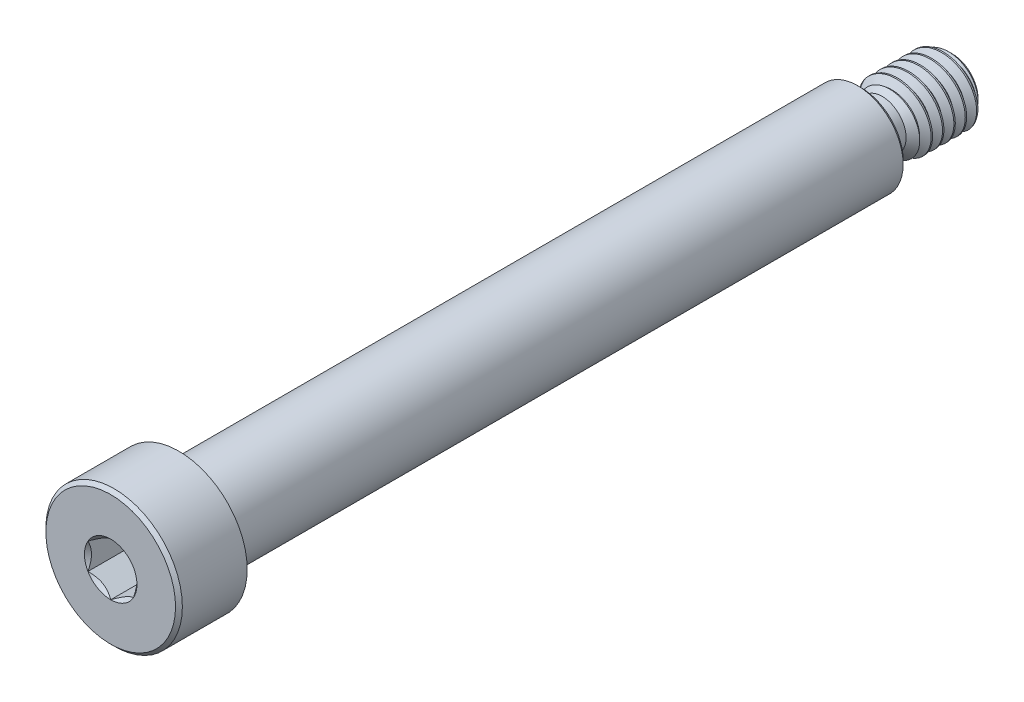
SolidWorks part; units mm, degrees
material "Alloy Steel"
ref_plane "Front Plane" through (0, 0, 0) normal (0, 0, 1) x (1, 0, 0)
ref_plane "Top Plane" through (0, 0, 0) normal (0, 1, 0) x (1, 0, 0)
ref_plane "Right Plane" through (0, 0, 0) normal (1, 0, 0) x (0, 0, -1)
sketch "Sketch2" plane through (0, 0, 0) normal (1, 0, 0) x (0, 0, -1)
  line L0 (-18.5, 0) -> (18.5, 0) construction
  line L1 (-18.5, 0) -> (-18.5, 3)
  line L2 (-18.5, 3) -> (-15.5, 3)
  line L3 (-15.5, 3) -> (-15.5, 2)
  line L4 (-15.5, 2) -> (14.5, 2)
  line L5 (14.5, 1.5) -> (18.5, 1.5)
  line L6 (18.5, 1.5) -> (18.5, 0)
  line L7 (18.4687, 1.5541) -> (18.7187, 1.1211) construction
  line L8 (18.7187, 1.1211) -> (18.9687, 1.5541) construction
  line L9 (18.9687, 1.5541) -> (18.4687, 1.5541) construction
  line L10 (18.5, 1.5) -> (18.9375, 1.5) construction
  line L11 (18.7187, 1.5541) -> (18.7187, 1.5) construction
  line L12 (18.7187, 1.5) -> (18.7187, 1.1752) construction
  line L13 (18.7187, 1.1752) -> (18.7187, 1.1211) construction
  line L14 (18.6875, 1.1752) -> (18.75, 1.1752)
  line L15 (18.4844, 1.5271) -> (18.9531, 1.5271)
  line L16 (18.75, 1.1752) -> (18.9531, 1.5271)
  line L17 (18.6875, 1.1752) -> (18.4844, 1.5271)
  line L18 (18.5, 0) -> (18.5, -1.5) construction
  line L19 (14.5, -2) -> (14.5, 0) construction
  line L20 (14.5, 0) -> (14.5, 2) construction
  line L21 (-18.5, 0) -> (-18.5, -3) construction
  line L22 (15.414, 1.05) -> (15.414, -1.05) construction
  line L23 (18.5, 0) -> (15.414, 0) construction
  ellipse E0 centre (16.957, 0) end of major axis (16.957, 0.6) minor radius 0.6 construction
  point P12 (17.25, -1.5)
  point P22 (18.7187, 1.5271)
  point P23 (10.5, 0)
  point P25 (-10.5, 0)
  point P26 (-15.5, -3)
  point P29 (14.5, -2)
  point P40 (15.414, 0)
  dimension "D1" = 1.25
  dimension "D3" = 8
  dimension "D4" = 8
  dimension "Shoulder Length" = 30
  dimension "D5" = 1.2
  dimension "D6" = 1.2
sketch "Sketch3" plane through (0, 0, 0) normal (0, 0, 1) x (1, 0, 0)
  line L1 (0, 1.1547) -> (-1, 0.5774)
  line L2 (-1, 0.5774) -> (-1, -0.5774)
  line L3 (-1, -0.5774) -> (0, -1.1547)
  line L4 (0, -1.1547) -> (1, -0.5774)
  line L5 (1, -0.5774) -> (1, 0.5774)
  line L6 (1, 0.5774) -> (0, 1.1547)
  circle A0 centre (0, 0) radius 1 construction
  dimension "Drive Size" = 2
sketch "Sketch4" plane through (0, 0, 0) normal (1, 0, 0) x (0, 0, -1)
  line L0 (-15.5, 3) -> (-18.35, 3)
  line L1 (-18.35, 3) -> (-18.5, 2.85)
  line L2 (-15.5, 3) -> (-15.5, 2)
  line L7 (-18.5, 0) -> (18.5, 0) construction
  line L8 (-15.5, 2) -> (14.3333, 2)
  line L9 (14.3333, 2) -> (14.5, 1.8333)
  line L10 (14.5, 1.8333) -> (14.5, 0)
  line L11 (14.5, 2) -> (14.5, 1.8333) construction
  line L12 (14.5, 1.8333) -> (14.5, 1.6667) construction
  line L13 (14.5, 1.6667) -> (14.5, 1.5) construction
  line L14 (-18.5, 2.85) -> (-18.5, 0)
  line L16 (-18.5, 0) -> (14.5, 0)
  line L18 (-18.5, 3) -> (-15.5, 3) construction
  dimension "D3" = 45
  dimension "D5" = 5.7
  dimension "D1" = 45
revolve "Revolve1" add sketch "Sketch4" angle 360 about L16
sketch "Sketch5" plane through (0, 0, 18.5) normal (0, 0, 1) x (1, 0, 0)
  line L0 (1, 0.5774) -> (0, 1.1547) construction
  line L1 (1, -0.5774) -> (1, 0.5774) construction
  line L2 (0, -1.1547) -> (1, -0.5774) construction
  line L3 (-1, -0.5774) -> (0, -1.1547) construction
  line L4 (-1, 0.5774) -> (-1, -0.5774) construction
  line L5 (0, 1.1547) -> (-1, 0.5774) construction
  line L6 (1, 0.5774) -> (0, 1.1547)
  line L7 (1, -0.5774) -> (1, 0.5774)
  line L8 (0, -1.1547) -> (1, -0.5774)
  line L9 (-1, -0.5774) -> (0, -1.1547)
  line L10 (-1, 0.5774) -> (-1, -0.5774)
  line L11 (0, 1.1547) -> (-1, 0.5774)
extrude "Cut-Extrude1" cut sketch "Sketch5" against normal blind 2.25
sketch "Sketch6" plane through (0, 0, 18.5) normal (0, 0, 1) x (1, 0, 0)
  circle A0 centre (0, 0) radius 1.1547
extrude "Cut-Extrude4" cut sketch "Sketch6" against normal blind 2.25 draft 45
sketch "Sketch7" plane through (0, 0, 0) normal (1, 0, 0) x (0, 0, -1)
  line L0 (14.5, 1.5) -> (18.125, 1.5)
  line L1 (14.5, 1.5) -> (18.5, 1.5) construction
  line L2 (18.125, 1.5) -> (18.5, 1.125)
  line L3 (18.5, 1.5) -> (18.5, 0) construction
  line L4 (18.5, 1.125) -> (18.5, 0)
  line L5 (18.5, 0) -> (14.5, 0)
  line L6 (14.5, -1.8333) -> (14.5, 1.8333) construction
  line L7 (14.5, 0) -> (14.5, 1.5)
  dimension "D1" = 45
  dimension "D2" = 0.375
revolve "Revolve2" add sketch "Sketch7" angle 360 about L5
sketch "Sketch10" plane through (0, 0, 0) normal (1, 0, 0) x (0, 0, -1)
  line L0 (14.725, 1.05) -> (15.414, 1.05)
  line L1 (15.414, 1.05) -> (16.364, 2)
  line L2 (16.364, 2) -> (14.5, 2)
  line L3 (14.5, 2) -> (14.5, 1.275)
  line L5 (18.5, 0) -> (14.5, 0) construction
  line L6 (-18.5, 0) -> (18.5, 0) construction
  line L7 (-15.5, 2) -> (14.5, 2) construction
  line L12 (-15.5, 2) -> (-15.1, 2)
  line L13 (-15.5, 2) -> (-15.5, 1.9)
  line L14 (-15.5, 1.9) -> (-15.2, 1.9)
  line L15 (-15.1, 2) -> (-15.2, 1.9)
  line L16 (14.725, 1.05) -> (14.725, 1.275) construction
  line L17 (14.725, 1.275) -> (14.725, 1.5) construction
  line L18 (18.125, 1.5) -> (14.5, 1.5) construction
  arc A0 (14.5, 1.275) -> (14.725, 1.05) centre (14.725, 1.275) ccw
  dimension "D3" = 45
  dimension "D4" = 45
  dimension "D5" = 3.8
  dimension "D1" = 0.3
revolve "Cut-Revolve1" cut sketch "Sketch10" angle 360 about L5
fillet "Fillet1" radius 0.05 1 edges at (-1.9, 0, 15.5)
sketch "Sketch15" plane through (0, 0, 0) normal (0, 0, 1) x (1, 0, 0)
  circle A0 centre (0, 0) radius 3 construction
sketch "Sketch8" plane through (0, 0, -18.5) normal (0, 0, -1) x (-1, 0, 0)
  circle A1 centre (0, 0) radius 1.5
curve "Helix/Spiral1" pitch 0.5 height 3.586 radius 1.5 centre (0, 0, -18.5) axis (0, 0, 1) start towards (0, 1, 0)
sketch "Sketch9" plane through (0, 0, 0) normal (1, 0, 0) x (0, 0, -1)
  line L0 (18.6875, 1.1752) -> (18.75, 1.1752) construction
  line L1 (18.75, 1.1752) -> (18.9531, 1.5271) construction
  line L2 (18.4844, 1.5271) -> (18.9531, 1.5271) construction
  line L3 (18.6875, 1.1752) -> (18.4844, 1.5271) construction
  line L4 (18.6875, 1.1752) -> (18.75, 1.1752)
  line L5 (18.75, 1.1752) -> (18.9531, 1.5271)
  line L6 (18.4844, 1.5271) -> (18.9531, 1.5271)
  line L7 (18.6875, 1.1752) -> (18.4844, 1.5271)
sweep "Cut-Sweep1" cut profiles "Sketch9" path "Helix/Spiral1"
equation "\"D2@Sketch2\" = \"Pitch@Sketch2\" / 8"
equation "\"D1@Sketch2\"=\"Pitch@Sketch2\"*2.5"
equation "\"D5@Sketch4\"=\"Head Diameter@Sketch2\"*0.95"
equation "\"D1@Cut-Extrude1\"=\"Head Height@Sketch2\"*0.75"
equation "\"D1@Cut-Extrude4\"=\"D1@Cut-Extrude1\""
equation "\"D2@Sketch7\" = \"Pitch@Sketch2\" * 0.75"
equation "\"D3@Helix/Spiral1\"=\"Thread Length@Sketch2\"-\"Flat@Sketch2\"+\"Pitch@Sketch2\""
equation "\"D4@Helix/Spiral1\"=\"Pitch@Sketch2\""
equation "\"D3@Sketch2\"=\"Thread Length@Sketch2\"*2"
equation "\"D4@Sketch2\"=\"D3@Sketch2\""
equation "\"D5@Sketch2\" = \"Thread Size@Sketch2\" * .4"
equation "\"D6@Sketch2\"=\"Thread Length@Sketch2\"*.3"
equation "\"Flat@Sketch2\"=\"Thread Length@Sketch2\"*0.2285"
equation "\"Flat OD@Sketch2\" = \"Thread Size@Sketch2\" * .7"
equation "\"D5@Sketch10\"=\"Shoulder Diameter@Sketch2\"*.95"
equation "\"D1@Fillet1\"=\"Shoulder Diameter@Sketch2\"*.0125"
equation "\"D1@Sketch10\"=\"Head Height@Sketch2\"*.1"
